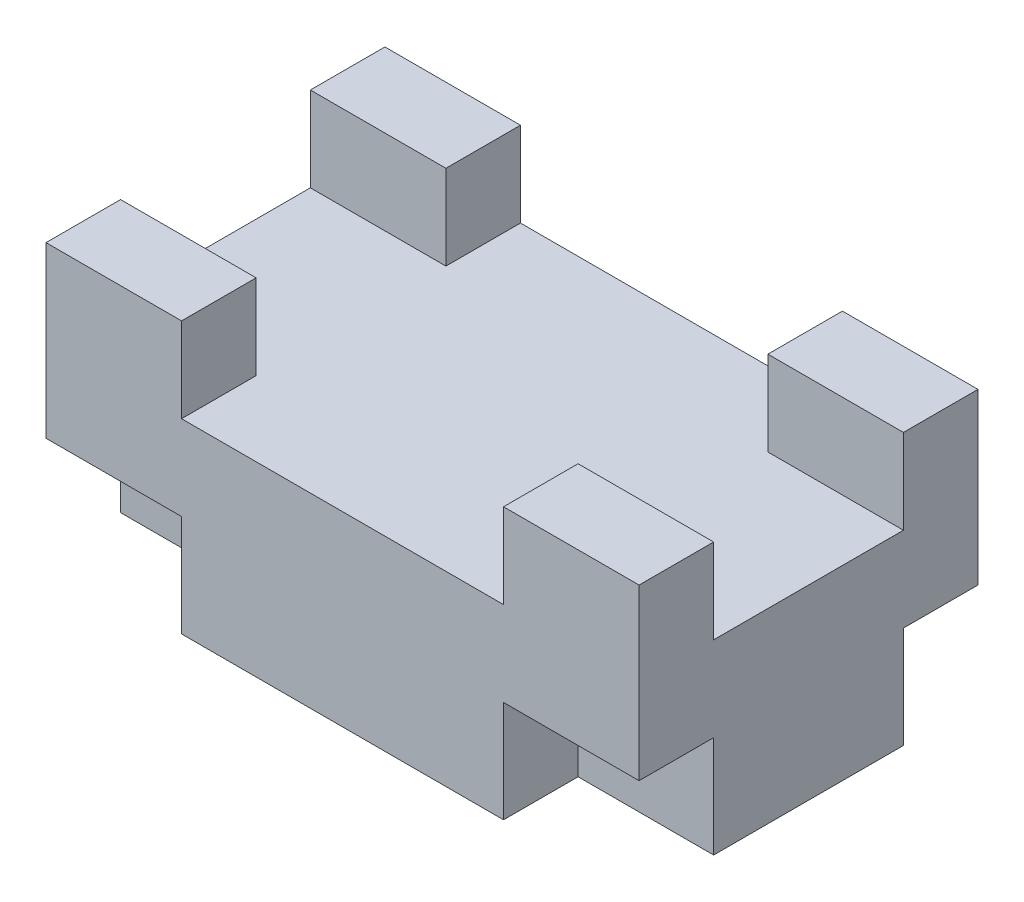
SolidWorks part; units mm, degrees
ref_plane "Front Plane" through (0, 0, 0) normal (0, 0, 1) x (1, 0, 0)
ref_plane "Top Plane" through (0, 0, 0) normal (0, 1, 0) x (1, 0, 0)
ref_plane "Right Plane" through (0, 0, 0) normal (1, 0, 0) x (0, 0, -1)
sketch "Sketch2" plane through (0, 0, 0) normal (0, 1, 0) x (1, 0, 0)
  line L0 (-87.5, 100) -> (-87.5, 0)
  line L1 (0, 0) -> (-175, 0)
  line L2 (0, 0) -> (0, 100)
  line L3 (0, 100) -> (-175, 100)
  line L4 (-175, 0) -> (-175, 100)
  line L5 (0, 50) -> (-175, 50)
  line L6 (-175, 100) -> (-135, 100)
  line L7 (-175, 100) -> (-175, 78)
  line L8 (-175, 78) -> (-135, 78)
  line L9 (-135, 100) -> (-135, 78)
  line L10 (-135, 0) -> (-135, 22)
  line L11 (-175, 22) -> (-135, 22)
  line L12 (-175, 22) -> (-175, 0)
  line L13 (-40, 0) -> (-40, 22)
  line L14 (0, 22) -> (-40, 22)
  line L15 (0, 78) -> (-40, 78)
  line L16 (-40, 100) -> (-40, 78)
  dimension "D1" = 175
  dimension "D2" = 100
  dimension "D3" = 40
  dimension "D4" = 22
extrude "Boss-Extrude1" add sketch "Sketch2" along normal blind 30 contours L3 L9 L8 L4 L5 L0 | L16 L3 L0 L5 L2 L15 | L4 L11 L10 L1 L0 L5 | L14 L2 L5 L0 L1 L13 region at (-49.73, 0, -71.475) region at (-125.27, 0, -71.475) region at (-49.73, 0, -28.525) region at (-125.27, 0, -28.525)
sketch "Sketch3" plane through (0, 30, 0) normal (0, 1, 0) x (1, 0, 0)
  line L0 (-175, 78) -> (-175, 100)
  line L1 (-135, 100) -> (-175, 100)
  line L3 (-175, 100) -> (0, 100)
  line L4 (-175, 100) -> (-175, 0)
  line L5 (-175, 0) -> (0, 0)
  line L6 (0, 100) -> (0, 0)
  line L7 (-175, 100) -> (-135, 100)
  line L8 (-175, 100) -> (-175, 78)
  line L9 (-175, 78) -> (-135, 78)
  line L10 (-135, 100) -> (-135, 78)
  line L11 (-40, 100) -> (0, 100)
  line L12 (-40, 100) -> (-40, 78)
  line L13 (-40, 78) -> (0, 78)
  line L14 (0, 100) -> (0, 78)
  line L15 (-175, 22) -> (-135, 22)
  line L16 (-175, 22) -> (-175, 0)
  line L17 (-175, 0) -> (-135, 0)
  line L18 (-135, 22) -> (-135, 0)
  line L19 (-40, 22) -> (0, 22)
  line L20 (-40, 22) -> (-40, 0)
  line L21 (-40, 0) -> (0, 0)
  line L22 (0, 22) -> (0, 0)
  line M6 (-135, 0) -> (-40, 0)
  line M7 (-40, 0) -> (-40, 22)
  line M8 (-40, 22) -> (0, 22)
  line M9 (0, 22) -> (0, 78)
  line M10 (0, 78) -> (-40, 78)
  line M11 (-40, 78) -> (-40, 100)
  line M12 (-40, 100) -> (-135, 100)
  line M13 (-135, 100) -> (-135, 78)
  line M14 (-135, 78) -> (-175, 78)
  line M15 (-175, 78) -> (-175, 22)
  line M16 (-175, 22) -> (-135, 22)
  line M17 (-135, 22) -> (-135, 0)
extrude "Boss-Extrude2" add sketch "Sketch3" along normal blind 25 contours L1 L0 M13 M14 | M17 M6 M7 M8 M9 M10 M11 M12 M13 M14 M15 M16 | L6 L3 M11 M10 | L6 L5 M8 M7 | L4 L5 M17 M16 region at (-87.5, 30, -50) region at (-155, 30, -89) region at (-155, 30, -11) region at (-20, 30, -89) region at (-20, 30, -11)
extrude "Boss-Extrude3" add sketch "Sketch3<3>" along normal blind 50 contours L1 L0 M13 M14 | L6 L3 M11 M10 | L6 L5 M8 M7 | L4 L5 M17 M16 region at (-155, 30, -89) region at (-155, 30, -11) region at (-20, 30, -89) region at (-20, 30, -11)
sketch "Sketch3<3>" plane through (0, 30, 0) normal (0, 1, 0) x (1, 0, 0) same geometry as "Sketch3"
